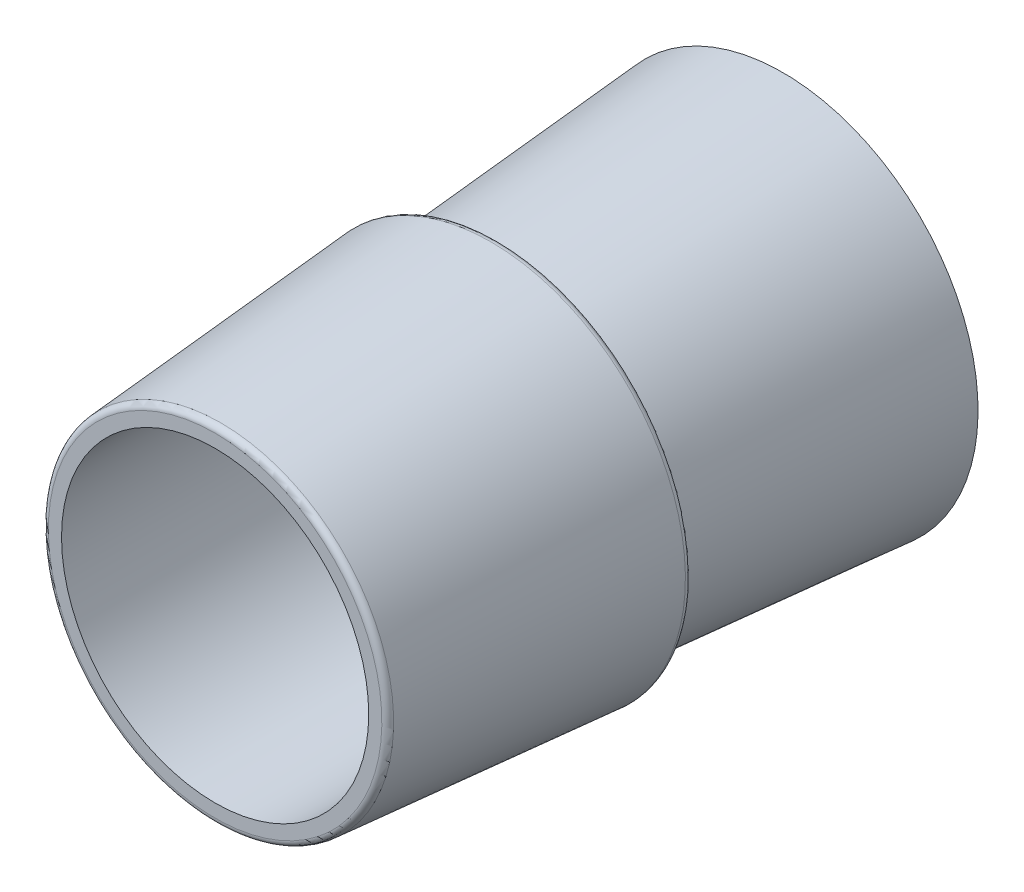
SolidWorks part; units mm, degrees
ref_plane "Front Plane" through (0, 0, 0) normal (0, 0, 1) x (1, 0, 0)
ref_plane "Top Plane" through (0, 0, 0) normal (0, 1, 0) x (1, 0, 0)
ref_plane "Right Plane" through (0, 0, 0) normal (1, 0, 0) x (0, 0, -1)
sketch "Sketch2" plane through (0, 0, 0) normal (1, 0, 0) x (0, 0, -1)
  line L0 (-0.6772, -1.5873) -> (8.5653, -1.5873)
  line L4 (-5.1845, 1.2262) -> (-0.6772, 1.5839) construction
  line L5 (-0.6772, 1.5839) -> (-0.6772, 1.2188) construction
  line L6 (-0.5813, 1.2264) -> (3.9226, 1.5839)
  line L7 (3.9226, 1.5839) -> (3.9226, 1.2188)
  line L8 (4.0185, 1.2264) -> (8.5653, 1.5873)
  line L9 (8.5653, 1.5873) -> (8.5653, -1.5873)
  line L10 (-5.1845, 1.2262) -> (-5.277, 1.2189)
  line L11 (-0.5813, 1.2264) -> (-0.6772, 1.2188)
  line L12 (4.0185, 1.2264) -> (3.9226, 1.2188)
  line L13 (-5.277, 1.2189) -> (-5.277, -1.5873) construction
  line L14 (-0.6772, 1.2188) -> (-0.6772, -1.5873)
  line L15 (-0.6772, -1.5873) -> (-5.277, -1.5873) construction
revolve "Revolve2" add sketch "Sketch2" angle 360 about L0 region at (0, -0.0907, -3.992)
sketch "Sketch3" plane through (0, 0, -8.5653) normal (0, 0, -1) x (-1, 0, 0)
  line L0 (0, 1.5873) -> (0, -4.7619) construction
  line L1 (-3.1746, -1.5873) -> (3.1746, -1.5873) construction
  circle A0 centre (0, -1.5873) radius 3.1746 construction
  circle A1 centre (0, -1.5873) radius 2.5
  dimension "D1" = 5
extrude "Cut-Extrude1" cut sketch "Sketch3" against normal through all
fillet "Fillet1" radius 0.1 2 edges at (0, -4.7585, -3.9226) (0, -4.3934, 0.6772)
